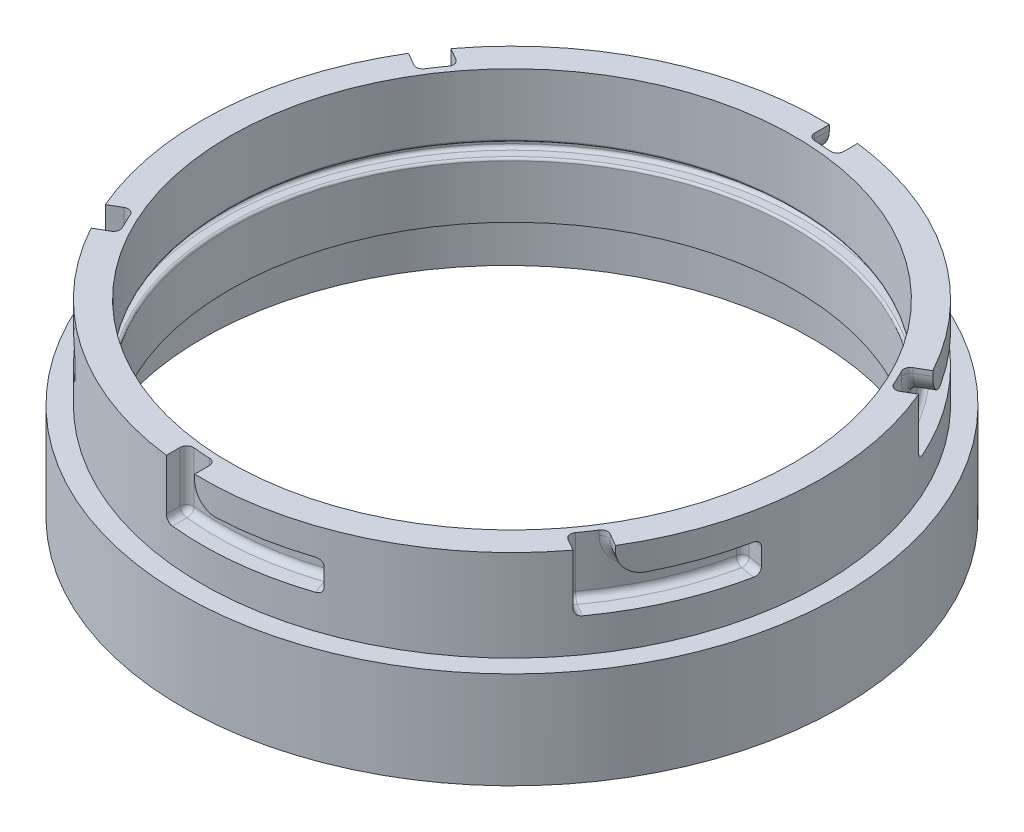
SolidWorks part; units mm, degrees
material "6061-T6 (SS)"
ref_plane "Front Plane" through (0, 0, 0) normal (0, 0, 1) x (1, 0, 0)
ref_plane "Top Plane" through (0, 0, 0) normal (0, 1, 0) x (1, 0, 0)
ref_plane "Right Plane" through (0, 0, 0) normal (1, 0, 0) x (0, 0, -1)
sketch "Sketch1" plane through (0, 0, 0) normal (0, 0, 1) x (1, 0, 0)
  line L0 (0, 60.758) -> (0, -61.3352) construction
  line L1 (71.12, 36.5125) -> (71.12, 15.5575)
  line L2 (71.12, 15.5575) -> (75.565, 15.5575)
  line L3 (75.565, 15.5575) -> (75.565, 6.0325)
  line L4 (75.565, 6.0325) -> (64.77, 6.0325)
  line L5 (64.77, 6.0325) -> (64.77, 18.7325)
  line L6 (64.77, 36.5125) -> (71.12, 36.5125)
  line L7 (64.77, 18.7325) -> (67.818, 18.7325)
  line L8 (67.818, 18.7325) -> (67.818, 21.9075)
  line L9 (67.818, 21.9075) -> (64.77, 21.9075)
  line L10 (64.77, 21.9075) -> (64.77, 36.5125)
  dimension "D1" = 6.35
  dimension "D2" = 9.525
  dimension "D3" = 30.48
  dimension "D4" = 71.12
  dimension "D5" = 75.565
  dimension "D6" = 3.048
  dimension "D7" = 12.7
  dimension "D8" = 15.875
revolve "Revolve1" add sketch "Sketch1" angle 360 about L0
sketch "Sketch2" plane through (0, 36.5125, 0) normal (0, 1, 0) x (1, 0, 0)
  line L0 (-8.6592, -70.5909) -> (-8.6592, -65.726)
  line L1 (-1.6742, -71.1003) -> (-1.6742, -66.2729)
  arc A0 (-1.6742, -71.1003) -> (-8.6592, -70.5909) centre (0, 0) cw
  circle A1 centre (0, 0) radius 71.12 construction
  arc A2 (-1.6742, -66.2729) -> (-8.6592, -65.726) centre (0, 0) cw
  dimension "D1" = 4.826
  dimension "D2" = 6.985
  dimension "D3" = 6.985
extrude "Cut-Extrude1" cut sketch "Sketch2" against normal blind 13.208
sketch "Sketch10" plane through (-1.6742, 0, 0) normal (-1, 0, 0) x (0, 0, 1)
  line L0 (66.2729, 23.3045) -> (66.2729, 30.2895)
  line L1 (66.2729, 23.3045) -> (66.2729, 36.5125) construction
  line L2 (66.2729, 30.2895) -> (71.1003, 30.2895)
  line L3 (71.1003, 23.3045) -> (71.1003, 36.5125) construction
  line L4 (71.1003, 30.2895) -> (71.1003, 23.3045)
  line L5 (71.1003, 23.3045) -> (66.2729, 23.3045)
  dimension "D1" = 6.985
ref_axis "Axis1" through (0, 6.0325, 0) along (0, 1, 0)
sketch "Sketch21" plane through (0, 23.3045, 0) normal (0, 1, 0) x (1, 0, 0)
  line L0 (-1.6742, -71.1003) -> (-1.6742, -66.2729) construction
  arc A0 (-1.6742, -73.5126) -> (73.4476, -3.5158) centre (0, 0) ccw
sketch "Sketch22" plane through (0, 23.3045, 0) normal (0, 1, 0) x (1, 0, 0)
  circle A1 centre (0, 0) radius 73.5317
sketch "Sketch23" plane through (0, 23.3045, 0) normal (0, 1, 0) x (1, 0, 0)
  arc A0 (-1.6742, -71.1003) -> (23.922, -66.9761) centre (0, 0) ccw
sweep "Cut-Sweep2" cut profiles "Sketch10" path "Sketch23"
fillet "Fillet1" radius 5.08 1 edges at (-1.6742, 30.2895, 68.6866)
fillet "Fillet7" radius 1.524 9 edges at (-1.6742, 35.941, 66.2729) (0.2383, 31.3979, 66.2936) (23.0569, 23.3045, 64.7227) (-8.6592, 23.3045, 68.1585) (23.0569, 30.2895, 64.7227) (22.1917, 26.797, 62.4694) (12.9344, 30.2895, 65.02) (6.9594, 23.3045, 65.9277) (-8.6592, 29.9085, 65.726)
pattern_circular "CirPattern1" count 6 over 360 about axis through (0, 60.758, 0) along (0, 1, 0) of "Fillet1", "Cut-Extrude1", "Cut-Sweep2", "Fillet7" reverse direction yes
fillet "Fillet2" radius 0.762 2 edges at (-67.818, 21.9075, 0) (-67.818, 18.7325, 0)
fillet "Fillet3" radius 0.508 2 edges at (-64.77, 18.7325, 0) (-64.77, 21.9075, 0)
sketch "Sketch24" plane through (0, 6.0325, 0) normal (0, -1, 0) x (1, 0, 0)
  line L0 (-2.0961, 67.1054) -> (-1.1566, 67.1033)
  line L1 (-1.6263, 67.1043) -> (-1.6325, 64.2837) construction
  line L2 (-3.1931, 64.513) -> (-0.071, 64.5062)
  spline S0 degree 3 poles (-2.0961, 67.1054) (-2.1672, 66.9295) (-2.2659, 66.6682) (-2.4002, 66.2739) (-2.4676, 66.0573) (-2.5063, 65.9255) knots 0 0 0 0 0.455486 0.670301 1 1 1 1
  spline S1 degree 3 poles (-2.5063, 65.9255) (-2.5773, 65.6449) (-2.6547, 65.2845) (-2.7636, 64.9081) (-2.7851, 64.7854) (-2.8051, 64.7157) (-2.8445, 64.6485) (-2.9065, 64.5845) (-3.0202, 64.5178) (-3.1269, 64.5162) (-3.1931, 64.513) knots 0 0 0 0 0.50758 0.647219 0.68628 0.726157 0.773713 0.821128 0.881401 1 1 1 1
  spline S2 degree 3 poles (-1.1566, 67.1033) (-1.0863, 66.9271) (-0.9887, 66.6654) (-0.8561, 66.2705) (-0.7897, 66.0536) (-0.7516, 65.9217) knots 0 0 0 0 0.455486 0.670301 1 1 1 1
  spline S3 degree 3 poles (-0.7516, 65.9217) (-0.6962, 65.7094) (-0.6454, 65.4407) (-0.5548, 65.1173) (-0.5157, 64.9486) (-0.4854, 64.8115) (-0.4614, 64.7227) (-0.4366, 64.6731) (-0.4076, 64.6316) (-0.3644, 64.5877) (-0.3091, 64.5493) (-0.2095, 64.5089) (-0.1255, 64.5109) (-0.071, 64.5062) knots 0 0 0 0 0.384807 0.478666 0.588978 0.688379 0.725395 0.749588 0.785292 0.813657 0.857185 0.902571 1 1 1 1
extrude "Cut-Extrude3" [suppressed] cut sketch "Sketch24" against normal blind 13.208
fillet "Fillet5" [suppressed] radius 0.508 tangent propagation no
fillet "Fillet6" [suppressed] radius 0.254
pattern_circular "CirPattern3" [suppressed] count 120 every 3 of bodies 114
sketch "Sketch25" plane through (0, 6.0325, 0) normal (0, -1, 0) x (1, 0, 0)
  circle A0 centre (0, 0) radius 75.565
  circle A1 centre (-1.0614, 0) radius 69.85
  dimension "D1" = 139.7
extrude "Boss-Extrude1" add sketch "Sketch25" along normal blind 12.7
